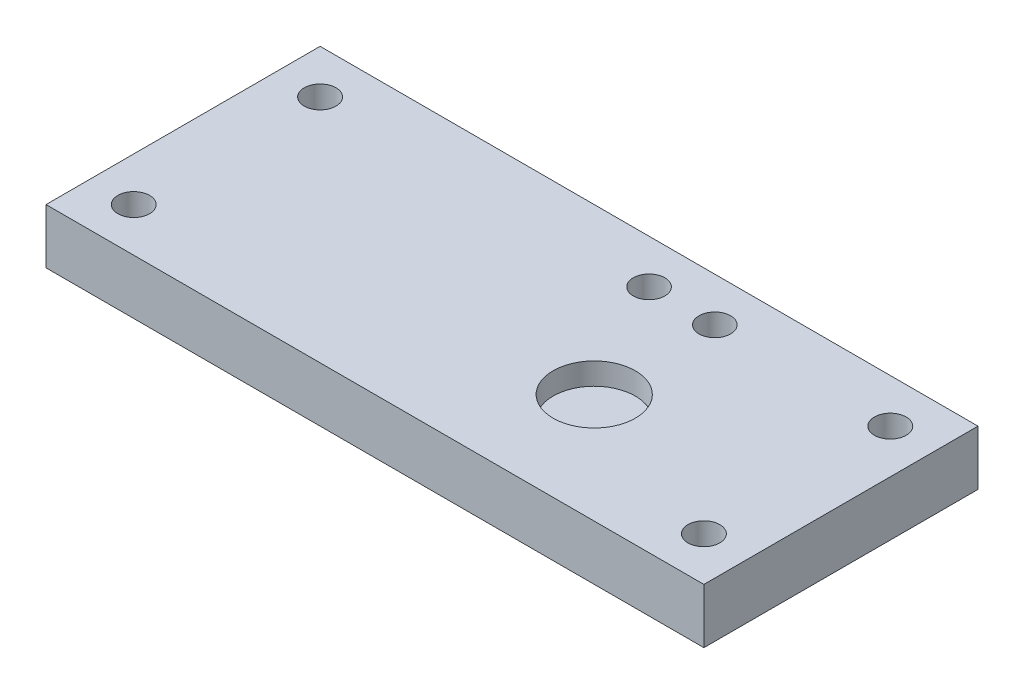
SolidWorks part; units mm, degrees
ref_plane "Front Plane" through (0, 0, 0) normal (0, 0, 1) x (1, 0, 0)
ref_plane "Top Plane" through (0, 0, 0) normal (0, 1, 0) x (1, 0, 0)
ref_plane "Right Plane" through (0, 0, 0) normal (1, 0, 0) x (0, 0, -1)
sketch "Sketch1" plane through (0, 0, 0) normal (0, 1, 0) x (1, 0, 0)
  line L1 (-38.1, 15.875) -> (38.1, 15.875)
  line L2 (-38.1, 15.875) -> (-38.1, -15.875)
  line L3 (-38.1, -15.875) -> (38.1, -15.875)
  line L4 (38.1, 15.875) -> (38.1, -15.875)
  line L5 (-38.1, 15.875) -> (38.1, -15.875) construction
  line L6 (-38.1, -15.875) -> (38.1, 15.875) construction
  point P0 (0, 0)
  dimension "D1" = 31.75
  dimension "D2" = 76.2
extrude "Boss-Extrude1" add sketch "Sketch1" along normal blind 6.35
sketch "Sketch2" plane through (0, 6.35, 0) normal (0, 1, 0) x (1, 0, 0)
  line L0 (-38.1, 15.875) -> (-38.1, -15.875) construction
  line L1 (38.1, 15.875) -> (-38.1, 15.875) construction
  line L2 (-38.1, -15.875) -> (38.1, -15.875) construction
  line L3 (38.1, -15.875) -> (38.1, 15.875) construction
  circle A0 centre (-33.02, 10.795) radius 1.8415
  circle A1 centre (-33.02, -10.795) radius 1.8415
  circle A2 centre (33.02, -10.795) radius 1.8415
  circle A3 centre (33.02, 10.795) radius 1.8415
  dimension "D3" = 3.683
  dimension "D1" = 5.08
  dimension "D2" = 5.08
  dimension "D4" = 5.08
  dimension "D5" = 5.08
extrude "Cut-Extrude1" cut sketch "Sketch2" against normal through all from offset 0
sketch "Sketch3" plane through (0, 6.35, 0) normal (0, 1, 0) x (1, 0, 0)
  line L0 (38.1, 15.875) -> (-38.1, 15.875) construction
  line L1 (38.1, -15.875) -> (38.1, 15.875) construction
  line L2 (-38.1, -15.875) -> (38.1, -15.875) construction
  circle A0 centre (12.7, -3.175) radius 4.7625
  circle A1 centre (5.08, 10.795) radius 1.8288
  circle A2 centre (12.7, 10.795) radius 1.8288
  point P6 (0, 0)
  point P11 (0, 0)
  dimension "D4" = 9.525
  dimension "D7" = 3.6576
  dimension "D1" = 5.08
  dimension "D2" = 12.7
  dimension "D3" = 25.4
  dimension "D5" = 7.62
  dimension "D6" = 33.02
extrude "Cut-Extrude2" cut sketch "Sketch3" against normal blind 2.54 contours A0 | A1 | A2 region at (12.7, 6.35, 3.175)
